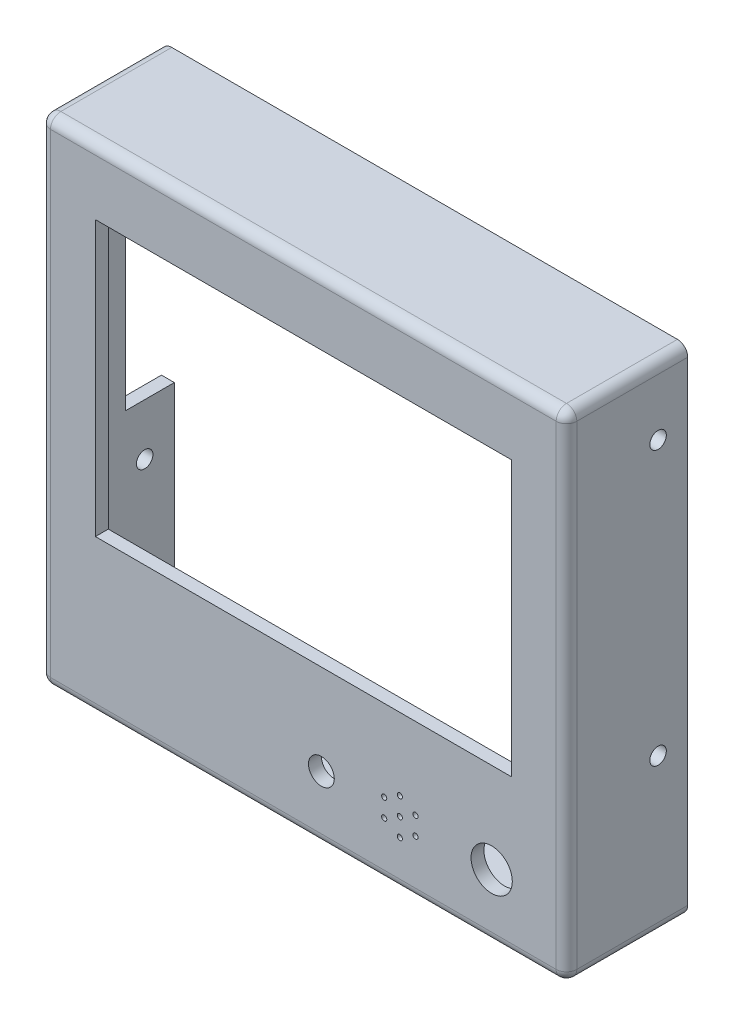
SolidWorks part; units mm, degrees
ref_plane "Top Plane" through (0, 0, 0) normal (0, 0, 1) x (1, 0, 0)
ref_plane "Front Plane" through (0, 0, 0) normal (0, 1, 0) x (1, 0, 0)
ref_plane "Right Plane" through (0, 0, 0) normal (1, 0, 0) x (0, 0, -1)
sketch "Face Sketch" plane through (0, 0, 0) normal (0, 0, 1) x (1, 0, 0)
  line L6 (-40.3, 35.2) -> (40.3, 35.2)
  line L7 (-40.3, 35.2) -> (-40.3, -18)
  line L8 (-40.3, -18) -> (40.3, -18)
  line L9 (40.3, 35.2) -> (40.3, -18)
  line L19 (0, 43.5) -> (0, 48) construction
  line L28 (-51, 48) -> (51, 48)
  line L29 (51, 48) -> (51, -48)
  line L30 (-51, -48) -> (51, -48)
  line L31 (-51, 48) -> (-51, -48)
  line L44 (-46.5, 43.5) -> (46.5, 43.5) construction
  line L45 (-46.5, 43.5) -> (-46.5, -43.5) construction
  line L46 (-46.5, -43.5) -> (46.5, -43.5) construction
  line L47 (46.5, 43.5) -> (46.5, -43.5) construction
  line L48 (0, -43.5) -> (0, 43.5) construction
  line L49 (-46.5, 0) -> (46.5, 0) construction
  line L50 (46.5, 0) -> (51, 0) construction
  circle A6 centre (-44, 41) radius 1.6 construction
  circle A7 centre (44, 41) radius 1.6 construction
  circle A8 centre (44, -24) radius 1.6 construction
  circle A9 centre (-44, -24) radius 1.6 construction
  circle A10 centre (18.7, -35.5) radius 0.5
  circle A19 centre (-38.35, -33.8096) radius 2.5 construction
  circle A20 centre (3.5, -35.5) radius 2.5
  circle A21 centre (36.5, -35.5) radius 4
  circle A22 centre (18.7, -32) radius 0.5
  circle A23 centre (21.7311, -33.75) radius 0.5
  circle A24 centre (21.7311, -37.25) radius 0.5
  circle A25 centre (18.7, -39) radius 0.5
  circle A26 centre (15.6689, -37.25) radius 0.5
  circle A27 centre (15.6689, -33.75) radius 0.5
  point P14 (0, 35.2)
  point P16 (51, 0)
  point P43 (18.7, -35.5)
  point P121 (0, 0)
  dimension "D12" = 3.2
  dimension "D17" = 1
  dimension "D24" = 5
  dimension "D28" = 5
  dimension "D20" = 8
  dimension "D4" = 65
  dimension "D5" = 88
  dimension "D9" = 53.2
  dimension "D10" = 93
  dimension "D11" = 87
  dimension "D18" = 10
  dimension "D19" = 8
  dimension "D29" = 3.5
  dimension "D6" = 4.5
  dimension "D15" = 8.3
  dimension "D16" = 9.6904
  dimension "D22" = 8.15
  dimension "D23" = 8
  dimension "D25" = 8
  dimension "D27" = 43
  dimension "D26" = 27.8
  dimension "D13" = 2.5
  dimension "D14" = 2.5
  dimension "D7" = 80.6
  dimension "D30" = 6
extrude "Face Extrude" add sketch "Face Sketch" along normal blind 2.5
sketch "Walls Sketch" plane through (0, 0, 0) normal (0, 0, -1) x (-1, 0, 0)
  line L10 (-48.5, 45.5) -> (48.5, 45.5)
  line L15 (-51, 48) -> (51, 48)
  line L16 (-51, 48) -> (-51, -48)
  line L17 (-51, -48) -> (51, -48)
  line L18 (51, 48) -> (51, -48)
  line L19 (48.5, 45.5) -> (48.5, -45.5)
  line L20 (-48.5, -45.5) -> (48.5, -45.5)
  line L21 (-48.5, 45.5) -> (-48.5, -45.5)
  dimension "D1" = 2.5
extrude "Walls Extrude" add sketch "Walls Sketch" along normal blind 21
sketch "SD Card Access Sketch" plane through (-51, 0, 0) normal (-1, 0, 0) x (0, 0, 1)
  line L0 (-9.25, 48) -> (-9.25, 7.5) construction
  line L1 (2.5, 48) -> (-21, 48) construction
  line L3 (-21, 23) -> (-11.5, 23)
  line L4 (-21, 23) -> (-21, -8)
  line L5 (-21, -8) -> (-11.5, -8)
  line L6 (-11.5, 23) -> (-11.5, -8)
  line L7 (-21, -48) -> (-21, 48) construction
  line L8 (2.5, 48) -> (2.5, -48) construction
  line L10 (-9.25, 7.5) -> (-11.5, 7.5) construction
  dimension "D1" = 31
  dimension "D3" = 40.5
  dimension "D4" = 14
extrude "SD Card Cut" cut sketch "SD Card Access Sketch" against normal blind 2.5
fillet "Edge Radius" radius 2 8 edges at (-51, 0, 2.5) (51, 0, 2.5) (0, -48, 2.5) (0, 48, 2.5) (-51, 48, -9.25) (51, 48, -9.25) (51, -48, -9.25) (-51, -48, -9.25)
sketch "Top Connectors Sketch" plane through (0, 0, 0) normal (1, 0, 0) x (0, 0, -1)
  line L0 (15.25, 43.5) -> (21, 43.5) construction
  line L1 (21, 23) -> (21, 46) construction
  line L2 (15.25, 41) -> (21, 41) construction
  line L3 (15.25, 8.5) -> (21, 8.5) construction
  circle A0 centre (15.25, 35) radius 1.6
  circle A1 centre (15.25, -18) radius 1.6
  dimension "D6" = 3.2
  dimension "D1" = 5.75
  dimension "D2" = 35
  dimension "D3" = 43.5
  dimension "D4" = 2.5
  dimension "D5" = 32.5
extrude "Top Connectors Cut" cut sketch "Top Connectors Sketch" against normal through all and the other way through all
equation "\"Controller Clearance\"= 2mm"
equation "\"Shell Thickness\"= 2.5"
equation "\"D6@Face Sketch\"=\"Controller Clearance\"+\"Shell Thickness\""
equation "\"Screen Clearance\"= 1mm"
equation "\"D15@Face Sketch\"=9.3-\"Screen Clearance\""
equation "\"PCB Hole Spacing X\"= 88mm"
equation "\"PCB Hole Spacing Y\"= 65mm"
equation "\"D5@Face Sketch\"=\"PCB Hole Spacing X\""
equation "\"D4@Face Sketch\"=\"PCB Hole Spacing Y\""
equation "\"Controller Size X\"= 93mm"
equation "\"Controller Size Y\"= 87mm"
equation "\"D11@Face Sketch\"=\"Controller Size Y\""
equation "\"D10@Face Sketch\"=\"Controller Size X\""
equation "\"Outside Fillet Radius\"= 2mm"
equation "\"D1@Edge Radius\"=\"Outside Fillet Radius\""
equation "\"Screen Height\"= 51.2mm"
equation "\"Screen Width\"= 78.6mm"
equation "\"D9@Face Sketch\"=\"Screen Height\"+2*\"Screen Clearance\""
equation "\"D7@Face Sketch\"=\"Screen Width\"+2*\"Screen Clearance\""
equation "\"SD Card Position\"= 22.5mm + 27/2.0mm + \"Shell Thickness\" + \"Controller Clearance\""
equation "\"SD Card Width\"= 31mm"
equation "\"D3@SD Card Access Sketch\"=\"SD Card Position\""
equation "\"D1@SD Card Access Sketch\"=\"SD Card Width\""
equation "\"D1@Walls Extrude\"=23.5-\"Shell Thickness\""
equation "\"D1@Face Extrude\"=\"Shell Thickness\""
equation "\"Top Mounting Hole Position\"= 2.5mm"
equation "\"Top Connector Y Position\"= 0.5 * \"Controller Size Y\" - \"Top Mounting Hole Position\" - 6"
equation "\"Standoff Height\"= 9 - \"Shell Thickness\""
equation "\"D1@Top Connectors Sketch\"=\"Standoff Height\" / 2 + \"Shell Thickness\""
equation "\"D2@Top Connectors Sketch\" = \"Top Connector Y Position\""
equation "\"D3@Top Connectors Sketch\" = \"Controller Size Y\" / 2"
equation "\"D4@Top Connectors Sketch\" = \"Top Mounting Hole Position\""
equation "\"D5@Top Connectors Sketch\" = \"PCB Hole Spacing Y\" / 2"
equation "\"Slip Fit Clearance\"= 0.15mm"
